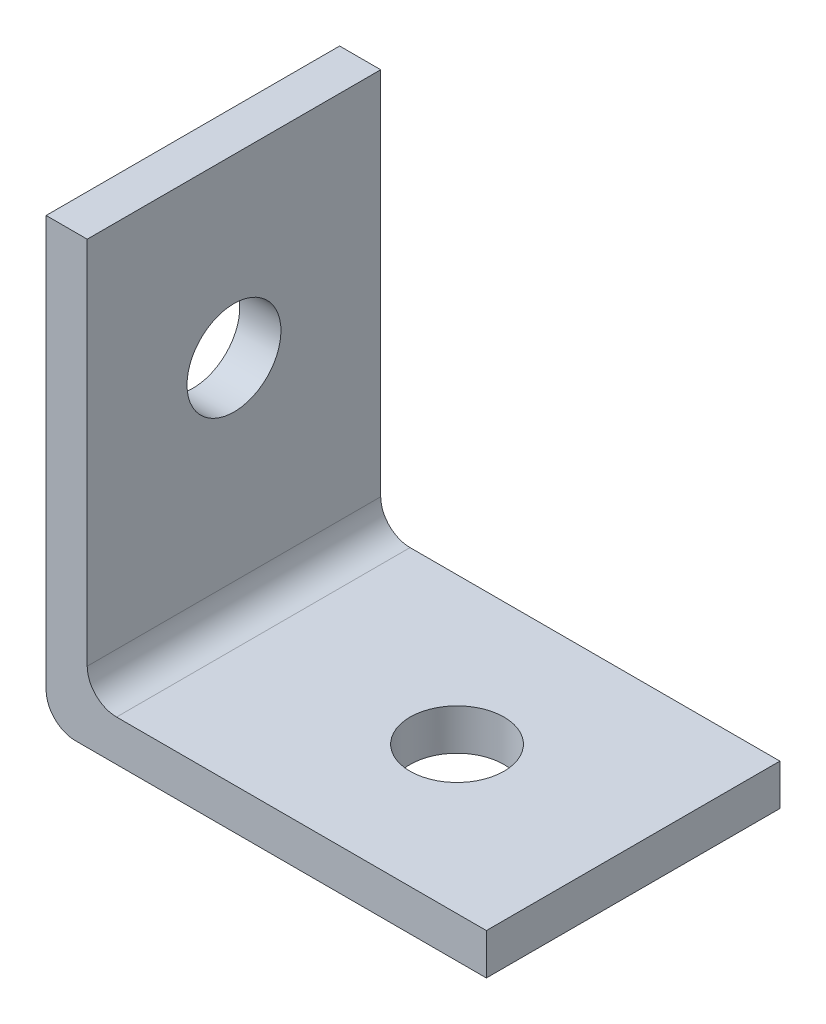
SolidWorks part; units mm, degrees
material "Plain Carbon Steel"
ref_plane "Front Plane" through (0, 0, 0) normal (0, 0, 1) x (1, 0, 0)
ref_plane "Top Plane" through (0, 0, 0) normal (0, 1, 0) x (1, 0, 0)
ref_plane "Right Plane" through (0, 0, 0) normal (1, 0, 0) x (0, 0, -1)
sketch "Sketch1" plane through (0, 0, 0) normal (0, 0, 1) x (1, 0, 0)
  line L0 (0, 0) -> (0, 19.05)
  line L1 (0, 19.05) -> (1.778, 19.05)
  line L2 (1.778, 19.05) -> (1.778, 1.778)
  line L3 (1.778, 1.778) -> (19.05, 1.778)
  line L4 (19.05, 1.778) -> (19.05, 0)
  line L5 (19.05, 0) -> (0, 0)
  dimension "D1" = 1.778
  dimension "D2" = 1.778
  dimension "D3" = 19.05
  dimension "D4" = 19.05
extrude "Boss-Extrude1" add sketch "Sketch1" against normal mid plane 12.7
sketch "Sketch2" plane through (0, 0, 0) normal (-1, 0, 0) x (0, 0, 1)
  line L0 (-6.35, 19.05) -> (6.35, 19.05) construction
  circle A0 centre (0, 11.43) radius 2.032
  dimension "D1" = 4.064
  dimension "D3" = 7.62
  dimension "D2" = 11.43
extrude "Cut-Extrude1" cut sketch "Sketch2" against normal up to next
sketch "Sketch3" plane through (0, 0, 0) normal (0, -1, 0) x (1, 0, 0)
  circle A0 centre (11.43, 0) radius 2.032
  dimension "D1" = 4.064
  dimension "D2" = 11.43
extrude "Cut-Extrude2" cut sketch "Sketch3" against normal up to next
fillet "Fillet2" radius 1.27 1 edges at (1.778, 1.778, 0)
fillet "Fillet3" radius 1.27 1 edges at (0, 0, 0)
